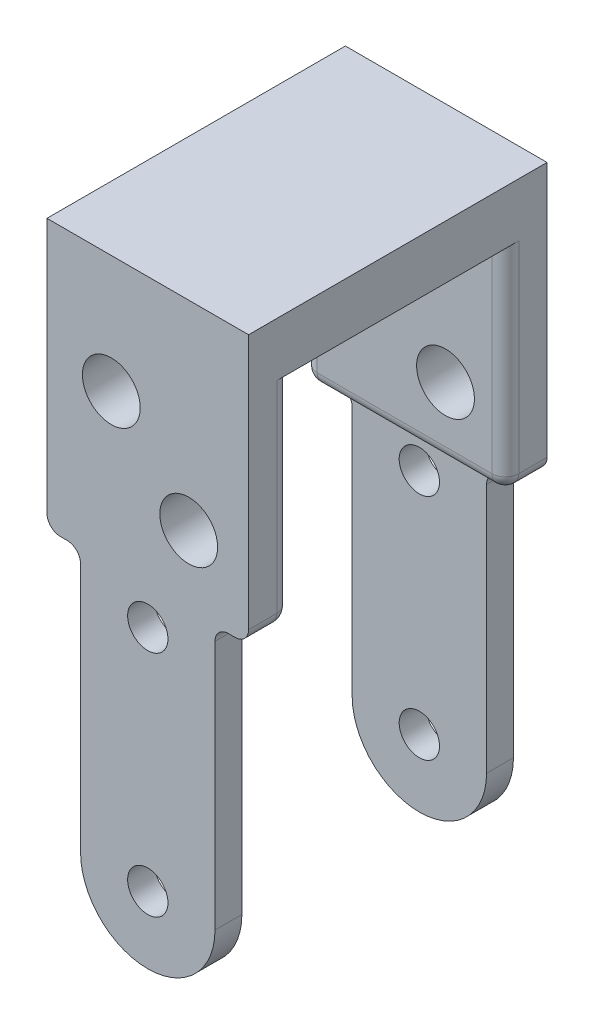
SolidWorks part; units mm, degrees
ref_plane "Front Plane" through (0, 0, 0) normal (0, 0, 1) x (1, 0, 0)
ref_plane "Top Plane" through (0, 0, 0) normal (0, 1, 0) x (1, 0, 0)
ref_plane "Right Plane" through (0, 0, 0) normal (1, 0, 0) x (0, 0, -1)
sketch "Sketch1" plane through (0, 0, 0) normal (0, 0, 1) x (1, 0, 0)
  line L0 (-8.6507, -36.3293) -> (-8.6507, -16.7293)
  line L1 (-8.6507, -16.7293) -> (1.3493, -16.7293)
  line L2 (1.3493, -16.7293) -> (1.3493, -36.3293)
  line L3 (1.3073, -16.8293) -> (-30.6927, -16.8293) construction
  circle A0 centre (-3.6507, -19.3293) radius 1.5 construction
  circle A1 centre (-3.6507, -19.3293) radius 1.5
  circle A2 centre (-3.6507, -36.3293) radius 1.5 construction
  circle A3 centre (-3.6507, -36.3293) radius 1.5
  arc A4 (1.3493, -36.3293) -> (-8.6507, -36.3293) centre (-3.6507, -36.3293) cw
  dimension "D1" = 5
  dimension "D2" = 0.1
extrude "Boss-Extrude1" add sketch "Sketch1" along normal blind 2 from offset 0.1
sketch "Sketch2" plane through (0, -16.7293, 0) normal (0, 1, 0) x (1, 0, 0)
  line L5 (-11.1507, 17) -> (3.8493, 17)
  line L6 (-11.1507, 17) -> (-11.1507, 1)
  line L7 (-11.1507, 1) -> (3.8493, 1)
  line L8 (3.8493, 17) -> (3.8493, 1)
  line L10 (-3.6507, -2.1) -> (-3.6507, -0.1) construction
  line L12 (-11.1507, -2.1) -> (3.8493, -2.1)
  line L13 (-11.1507, -2.1) -> (-11.1507, 20.1)
  line L14 (-11.1507, 20.1) -> (3.8493, 20.1)
  line L15 (3.8493, -2.1) -> (3.8493, 20.1)
  line L16 (1.3073, 9) -> (-30.6927, 9) construction
  line L17 (1.3493, -2.1) -> (-8.6507, -2.1) construction
  point P5 (-3.6507, 17)
  point P9 (-11.1507, 9)
  point P17 (-11.1507, 9)
  line M5 (1.3493, -0.1) -> (-8.6507, -0.1)
  line M6 (-8.6507, -0.1) -> (-8.6507, -2.1)
  line M7 (-8.6507, -2.1) -> (1.3493, -2.1)
  line M8 (1.3493, -2.1) -> (1.3493, -0.1)
  dimension "D1" = 16
  dimension "D2" = 15
extrude "Boss-Extrude2" add sketch "Sketch2" along normal blind 16 contours L5 L15 L14 L13 | L12 L15 L7 L13 M6 M5 M8 | M8 M5 M6 M7 region at (-3.6507, -16.7293, -18.55) region at (-3.6507, -16.7293, -0.8468) region at (-3.6507, -16.7293, 1.1)
sketch "Sketch3" plane through (0, -0.7293, 0) normal (0, 1, 0) x (1, 0, 0)
  line L1 (-11.1507, 20.1) -> (3.8493, 20.1)
  line L2 (-11.1507, 20.1) -> (-11.1507, -2.1)
  line L3 (-11.1507, -2.1) -> (3.8493, -2.1)
  line L4 (3.8493, 20.1) -> (3.8493, -2.1)
extrude "Boss-Extrude3" add sketch "Sketch3" along normal blind 4
extrude "Boss-Extrude4" add sketch "Sketch1<3>" along normal blind 2 from surface starting at face at (-3.6507, -6.7293, -20.1)
sketch "Sketch1<3>" plane through (0, 0, 0) normal (0, 0, 1) x (1, 0, 0) same geometry as "Sketch1"
fillet "Fillet1" radius 1 8 edges at (3.8493, -16.7293, -18.55) (1.3493, -16.7293, -19.1) (-8.6507, -16.7293, -19.1) (-11.1507, -16.7293, -18.55) (-11.1507, -16.7293, 0.55) (-8.6507, -16.7293, 1.1) (1.3493, -16.7293, 1.1) (3.8493, -16.7293, 0.55)
fillet "Fillet2" radius 1 10 edges at (-11.1507, -8.2293, -1) (-10.8578, -16.4364, -1) (3.8493, -8.2293, -1) (3.5564, -16.4364, -1) (-11.1507, -8.2293, -17) (-10.8578, -16.4364, -17) (3.8493, -8.2293, -17) (3.5564, -16.4364, -17) (-3.6507, -16.7293, -1) (-3.6507, -16.7293, -17)
hole_wizard "Ø4.0mm Dowel Hole1" positions "3DSketch1" profile "Sketch4" hole size "Ø4.0" standard "ANSI Metric" end condition through all
sketch3d "3DSketch1"
  point P0 (-6.3641, -5.4748, -20.1)
  point P2 (-0.6046, -11.5679, -20.1)
  point P5 (-4.7982, -5.2577, -20.1)
  point P6 (-6.3352, -4.3379, -20.1)
  point P7 (-6.3641, -5.4748, -20.1)
  point P8 (-0.6046, -11.5679, -20.1)
  point P9 (0, 0, 0)
sketch "Sketch4" plane through (-6.3641, -5.4748, -20.1) normal (1, 0, 0) x (0, 1, 0)
  line L0 (0, 0) -> (0, 22.2)
  line L1 (0, 22.2) -> (2.15, 22.2)
  line L2 (2.15, 22.2) -> (2.15, 0)
  line L5 (2.15, 0) -> (0, 0)
  line L11 (0, -6.35) -> (0, 107.95) construction
  dimension "Thru Hole Dia." = 4.3
  dimension "Thru Hole Depth" = 22.2
